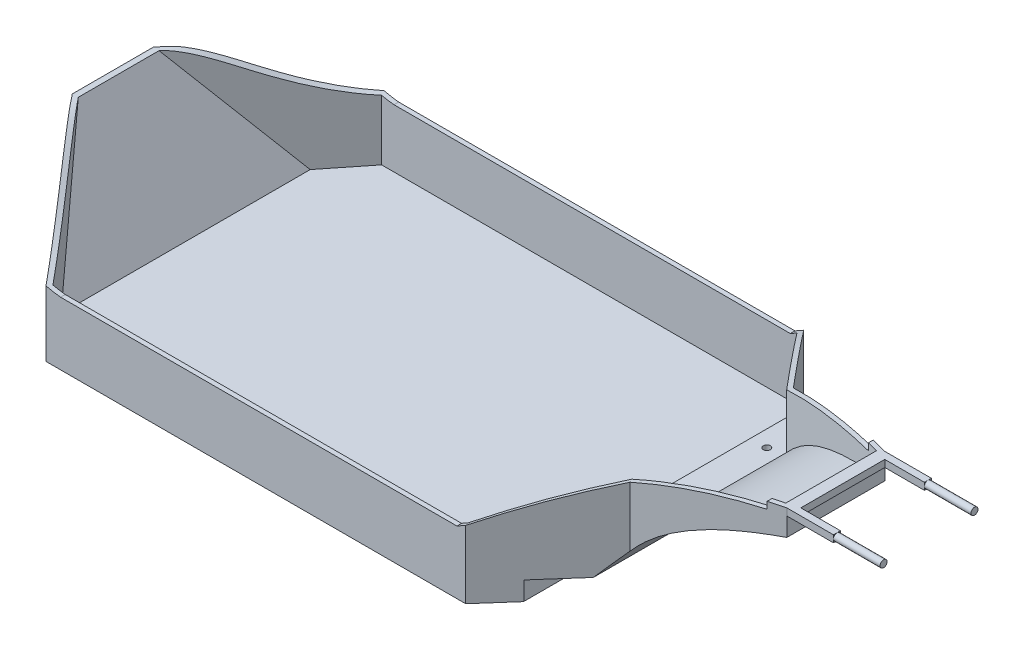
SolidWorks part; units mm, degrees
ref_plane "Front Plane" through (0, 0, 0) normal (0, 0, 1) x (1, 0, 0)
ref_plane "Top Plane" through (0, 0, 0) normal (0, 1, 0) x (1, 0, 0)
ref_plane "Right Plane" through (0, 0, 0) normal (1, 0, 0) x (0, 0, -1)
sketch "Sketch2" plane through (0, 0, 0) normal (0, 1, 0) x (1, 0, 0)
  line L1 (-106.7221, -72.5) -> (73.2779, -72.5)
  line L2 (-150.4619, -17.5) -> (-150.4619, 17.5)
  line L3 (-106.7221, 72.5) -> (73.2779, 72.5)
  line L4 (159.5381, -21) -> (159.5381, 21)
  line L5 (-150.4619, -72.5) -> (146.3174, 70.503) construction
  line L6 (-150.4619, 72.5) -> (154.1653, -74.2845) construction
  line L8 (-150.4619, 0) -> (265.3817, 0) construction
  line L9 (73.2779, 72.5) -> (106.3497, 35)
  line L10 (106.3497, 35) -> (159.5381, 21)
  line L11 (73.2779, -72.5) -> (106.3497, -35)
  line L12 (106.3497, -35) -> (159.5381, -21)
  line L13 (106.3497, 35) -> (106.3497, -35) construction
  line L14 (-106.7221, -72.5) -> (-150.4619, -17.5)
  line L15 (-150.4619, 17.5) -> (-106.7221, 72.5)
  point P0 (0, 0)
  point P12 (159.5381, 0)
  point P19 (-150.4619, 0)
  dimension "D1" = 310
  dimension "D2" = 145
  dimension "D3" = 42
  dimension "D4" = 50
  dimension "D5" = 55
  dimension "D6" = 145
  dimension "D7" = 55
  dimension "D8" = 50
  dimension "D9" = 70
  dimension "D10" = 180
  dimension "D11" = 180
  dimension "D12" = 35
extrude "Boss-Extrude1" add sketch "Sketch2" along normal blind 50
sketch "Sketch4" plane through (0, 0, -72.5) normal (0, 0, -1) x (-1, 0, 0)
  line L0 (-69.5381, 27) -> (100.4619, 27)
  line L1 (-73.2779, 0) -> (106.7221, 0) construction
  line L2 (150.4619, 50) -> (120.4619, 0)
  line L3 (106.7221, 0) -> (150.4619, 0) construction
  line L4 (120.4619, 0) -> (-84.5381, 0)
  line L5 (-106.3497, 0) -> (-73.2779, 0) construction
  line L6 (-159.5381, 50) -> (-159.5381, 42)
  line L7 (-159.5381, 50) -> (-159.5381, 0) construction
  line L8 (-159.5381, 42) -> (-159.5381, 0)
  line L9 (-159.5381, 0) -> (-84.5381, 0)
  line L10 (120.4619, 0) -> (150.4619, 0)
  line L11 (150.4619, 0) -> (150.4619, 50)
  line L12 (-159.5381, 50) -> (150.4619, 50)
  spline S0 degree 3 poles (100.4619, 27) (115.9803, 28.5555) (145.3554, 53.0462) (147.8197, 49.4316) (150.4619, 50) knots 0 0 0 0 0.398736 1 1 1 1
  spline S1 degree 3 poles (-159.5381, 42) (-94.8798, 30.8176) (-108.4066, 2.7607) (-84.5381, 0) knots 0 0 0 0 1 1 1 1
  spline S2 degree 2 poles (-159.5381, 50) (-110.6024, 50.8465) (-69.5381, 27) knots 0 0 0 1 1 1
  line M9 (106.7221, 0) -> (106.7221, 50)
  line M10 (106.7221, 50) -> (-73.2779, 50)
  line M11 (-73.2779, 50) -> (-73.2779, 0)
  dimension "D3" = 170
  dimension "D1" = 27
  dimension "D2" = 20
  dimension "D4" = 30
  dimension "D5" = 205
  dimension "D6" = 8
extrude "Cut-Extrude1" cut sketch "Sketch4" against normal through all contours S1 L8 L9 | L12 S2 M11 | S2 L0 S0 M11 M9 M10 | S0 L12 M9 | L10 L11 L2 region at (-16.7451, 38.5183, -72.5) region at (93.4281, 43.8153, -72.5) region at (-119.9394, 42.076, -72.5) region at (-140.4619, 16.6667, -72.5) region at (133.4897, 16.5661, -72.5)
sketch "Sketch6" plane through (0, 0, -72.5) normal (0, 0, -1) x (-1, 0, 0)
  line L0 (-104.9663, 8.0407) -> (-84.9663, 8.0521)
  line L1 (-84.9663, 8.0521) -> (-84.9617, 0.0522)
  line L3 (-84.9617, 0.0522) -> (-103.1996, 0.0633)
  line L4 (-103.1996, 0.0633) -> (-104.9663, 8.0407)
  spline S0 degree 3 poles (-84.5381, 0) (-96.267, 1.3566) (-98.966, 8.8215) (-106.3497, 17.3908) knots 0 0 0 0 0.491397 0.491397 0.491397 0.491397 construction
  point P2 (-105.1287, 9.8984)
  point P3 (-104.9663, 8.0521)
  dimension "D1" = 8
  dimension "D3" = 20
extrude "Cut-Extrude2" cut sketch "Sketch6" against normal through all
shell "Shell2" thickness 2 removed face at (100.9177, 37.9277, -4.7009) removed face at (-121.4234, 36.9645, 2.3382) removed face at (-15.4619, 27, 0) removed face at (156.2016, 50, 0)
sketch "Sketch7" plane through (0.0046, 8.1008, 0) normal (-0.0006, -1, 0) x (1, -0.0006, 0)
  line L0 (84.9616, 0) -> (135.025, 0) construction
  line L1 (84.9616, 59.2518) -> (84.9616, -59.2518) construction
  circle A0 centre (89.9616, 40) radius 1.5
  circle A1 centre (89.9616, -40) radius 1.5
  dimension "D3" = 3
  dimension "D4" = 3
  dimension "D1" = 40
  dimension "D2" = 40
  dimension "D5" = 5
  dimension "D6" = 5
extrude "Cut-Extrude3" cut sketch "Sketch7" against normal through all
sketch "Sketch8" plane through (0, 50, 0) normal (0, 1, 0) x (1, 0, 0)
  line L0 (152.8651, 22.7564) -> (152.8651, 20.6883)
  line L1 (152.8651, 20.6883) -> (157.5381, 19.4583)
  line L2 (157.5381, 19.4583) -> (157.5381, -19.4583)
  line L3 (157.5381, -19.4583) -> (152.8651, -20.6883)
  line L4 (152.8651, -20.6883) -> (152.8651, -22.7564)
  line L5 (152.8651, -22.7564) -> (159.5381, -21)
  line L6 (159.5381, -21) -> (159.5381, 21)
  line L7 (159.5381, 21) -> (152.8651, 22.7564)
sketch "Sketch9" plane through (0, 50, 0) normal (0, 1, 0) x (1, 0, 0)
  line L0 (152.8651, 20.6883) -> (157.5381, 19.4583)
  line L1 (157.5381, 19.4583) -> (157.5381, -19.4583)
  line L2 (157.5381, -19.4583) -> (152.8651, -20.6883)
  line L3 (152.8651, -20.6883) -> (152.8651, -22.7564)
  line L4 (152.8651, -22.7564) -> (159.5381, -21)
  line L5 (159.5381, -21) -> (179.5381, -21)
  line L6 (179.5381, -21) -> (179.5381, -18)
  line L7 (179.5381, -18) -> (162.5381, -18)
  line L8 (162.5381, -18) -> (162.5381, 18)
  line L9 (162.5381, 18) -> (179.5381, 18)
  line L10 (152.8651, 20.6883) -> (152.8651, 22.7564)
  line L11 (152.8651, 22.7564) -> (159.5381, 21)
  line L12 (159.5381, 21) -> (179.5381, 21)
  line L13 (179.5381, 21) -> (179.5381, 18)
  line L14 (159.5381, -21) -> (159.5381, 21) construction
  dimension "D1" = 3
  dimension "D2" = 3
  dimension "D3" = 3
  dimension "D4" = 20
  dimension "D5" = 20
extrude "Boss-Extrude2" add sketch "Sketch9" along normal blind 3
sketch "Sketch10" plane through (179.5381, 0, 0) normal (1, 0, 0) x (0, 0, -1)
  line L0 (-21, 51.5) -> (-16.9142, 51.5) construction
  line L1 (-21, 53) -> (-21, 50) construction
  circle A0 centre (-19.5, 51.5) radius 1.5
extrude "Boss-Extrude3" add sketch "Sketch10" along normal blind 20
mirror "Mirror1" about plane through (0, 0, 0) normal (0, 0, 1) of "Boss-Extrude3"
